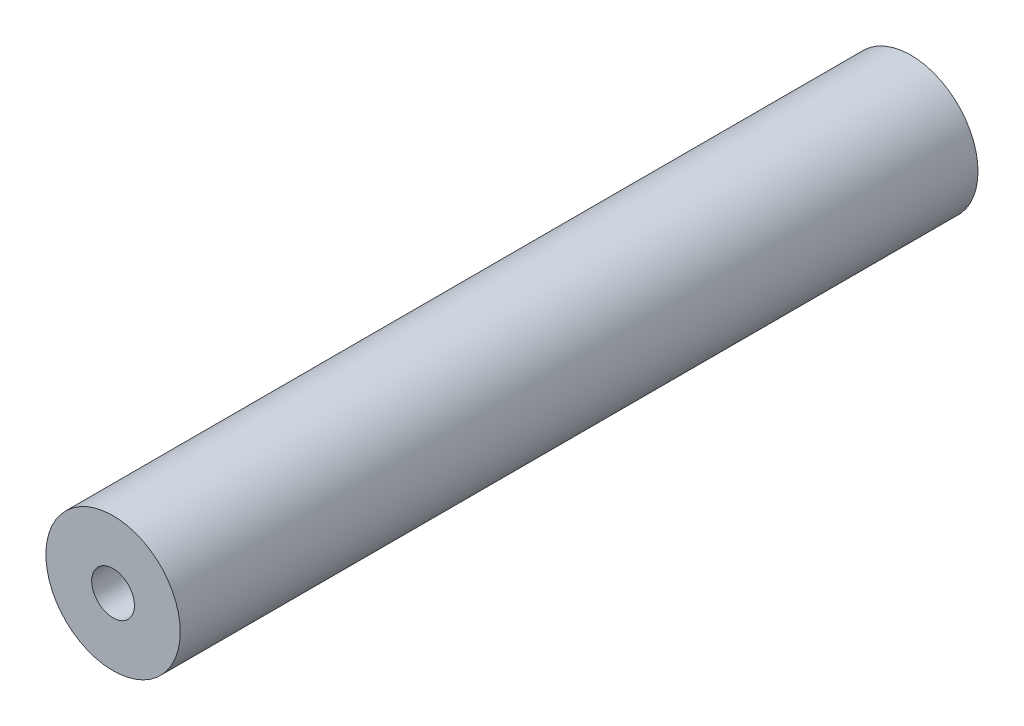
SolidWorks part; units mm, degrees
material "6061-T6 (SS)"
ref_plane "Front Plane" through (0, 0, 0) normal (0, 0, 1) x (1, 0, 0)
ref_plane "Top Plane" through (0, 0, 0) normal (0, 1, 0) x (1, 0, 0)
ref_plane "Right Plane" through (0, 0, 0) normal (1, 0, 0) x (0, 0, -1)
sketch "Sketch1" plane through (0, 0, 0) normal (0, 0, 1) x (1, 0, 0)
  circle A1 centre (0, 0) radius 6.35
  dimension "D2" = 12.7
extrude "Boss-Extrude1" add sketch "Sketch1" along normal mid plane 75.4062 contours A1 region at (0, 0, 0)
hole_wizard "#10-32 Tapped Hole1" positions "3DSketch1" profile "Sketch2" tap size "#10-32" standard "ANSI Inch"
sketch3d "3DSketch1"
  line L0 (0, 0, 37.7031) -> (0, 0, -37.7031) construction
  point P0 (0, 0, -37.7031)
  point P4 (0, 0, 37.7031)
sketch "Sketch2" plane through (0, 0, -37.7031) normal (1, 0, 0) x (0, 1, 0)
  line L0 (0, 0) -> (0, 13.2428)
  line L1 (0, 13.2428) -> (2.0193, 12.0294)
  line L2 (2.0193, 12.0294) -> (2.0193, 0)
  line L5 (2.0193, 0) -> (0, 0)
  line L10 (0, 13.2428) -> (-2.0193, 12.0294) construction
  line L11 (0, -6.35) -> (0, 107.95) construction
  dimension "Tap Drill Dia." = 4.0386
  dimension "Tap Drill Depth" = 12.0294
  dimension "Drill Angle" = 118
cosmetic thread "Hole Thread1"
cosmetic thread "Hole Thread2"
